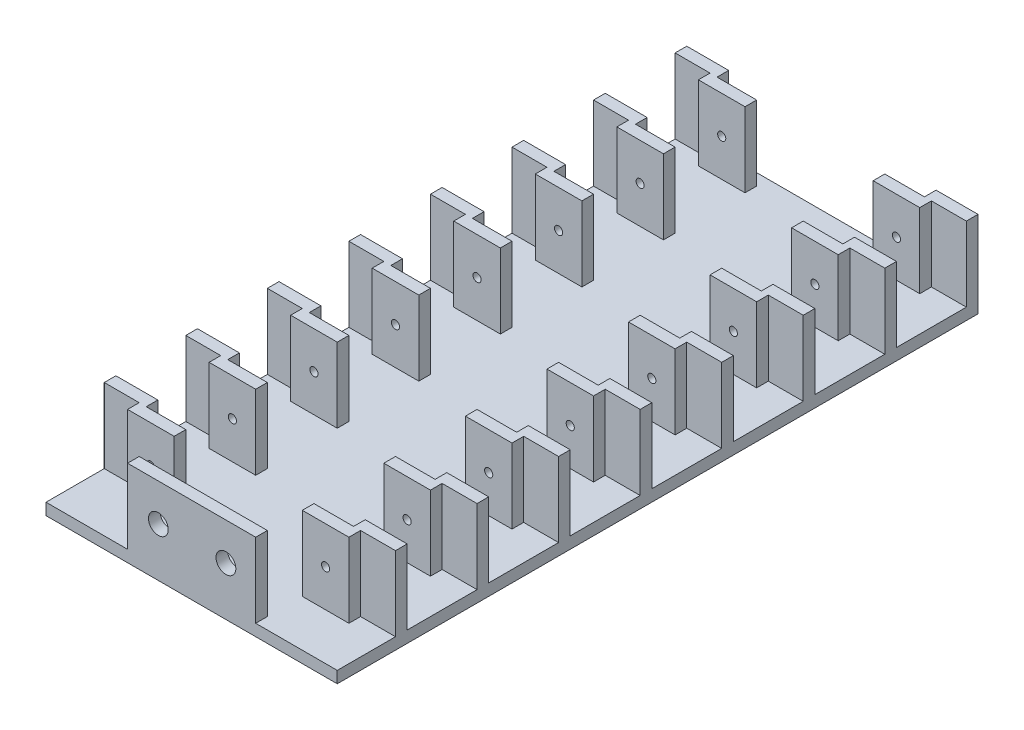
SolidWorks part; units mm, degrees
ref_plane "Front Plane" through (0, 0, 0) normal (0, 0, 1) x (1, 0, 0)
ref_plane "Top Plane" through (0, 0, 0) normal (0, 1, 0) x (1, 0, 0)
ref_plane "Right Plane" through (0, 0, 0) normal (1, 0, 0) x (0, 0, -1)
sketch "Sketch1" plane through (0, 0, 0) normal (0, 1, 0) x (1, 0, 0)
  line L0 (0, -138) -> (0, 138) construction
  line L1 (-14.5, 135) -> (-37.5, 135)
  line L2 (14.5, -135) -> (-14.5, -135)
  line L3 (14.5, -135) -> (14.5, 135) construction
  line L4 (14.5, 135) -> (-14.5, 135)
  line L5 (-14.5, -135) -> (-14.5, 135) construction
  line L6 (14.5, -135) -> (-14.5, 135) construction
  line L7 (14.5, 135) -> (-14.5, -135) construction
  line L8 (-37.5, 135) -> (-37.5, -135) construction
  line L9 (-37.5, -135) -> (-14.5, -135)
  line L10 (-37.5, 135) -> (-62.5, 135)
  line L11 (-62.5, 135) -> (-62.5, -135)
  line L12 (-62.5, -135) -> (-37.5, -135)
  line L13 (37.5, -135) -> (14.5, -135)
  line L14 (62.5, -135) -> (37.5, -135)
  line L15 (62.5, 135) -> (62.5, -135)
  line L16 (37.5, 135) -> (37.5, -135) construction
  line L17 (14.5, 135) -> (37.5, 135)
  line L18 (37.5, 135) -> (62.5, 135)
  point P0 (0, 0)
  point P4 (0, 0)
  dimension "D1" = 276
  dimension "D2" = 29
  dimension "D3" = 23
  dimension "D4" = 125
extrude "Boss-Extrude1" add sketch "Sketch1" along normal blind 5
sketch "Sketch2" plane through (0, 5, 0) normal (0, 1, 0) x (1, 0, 0)
  line L0 (62.5, -135) -> (62.5, 135) construction
  line L1 (-62.5, -135) -> (62.5, -135)
  line L2 (-62.5, -135) -> (-62.5, -130)
  line L3 (-62.5, -130) -> (62.5, -130)
  line L4 (62.5, -135) -> (62.5, -130)
  line L5 (-62.5, 135) -> (-37.5, 135) construction
  line L6 (-62.5, 135) -> (62.5, 135) construction
  line L7 (-62.5, 135) -> (-62.5, 130) construction
  line L8 (-62.5, 130) -> (62.5, 130) construction
  line L9 (62.5, 135) -> (62.5, 130) construction
  line L10 (-37.5, 135) -> (-27.5, 135)
  line L11 (-37.5, 135) -> (-47.5, 135)
  line L12 (-47.5, 135) -> (-47.5, 130)
  line L13 (-47.5, 130) -> (-27.5, 130)
  line L14 (-27.5, 130) -> (-27.5, 135)
  line L15 (0, 135) -> (0, 130) construction
  line L16 (47.5, 130) -> (27.5, 130)
  line L17 (47.5, 135) -> (47.5, 130)
  line L18 (37.5, 135) -> (47.5, 135)
  line L19 (37.5, 135) -> (27.5, 135)
  line L20 (27.5, 130) -> (27.5, 135)
  line L21 (-27.5, 130) -> (-27.5, -130) construction
  dimension "D1" = 5
  dimension "D2" = 5
  dimension "D3" = 25
  dimension "D4" = 10
  dimension "D5" = 10
extrude "Boss-Extrude2" add sketch "Sketch2" along normal blind 32
sketch "Sketch3" plane through (0, 0, 135) normal (0, 0, 1) x (1, 0, 0)
  line L0 (0, 37) -> (0, 0) construction
  line L1 (-62.5, 37) -> (62.5, 37) construction
  line L2 (-62.5, 37) -> (-62.5, 5) construction
  line L5 (-62.5, 37) -> (-62.5, 0) construction
  line L6 (-62.5, 21) -> (62.5, 21) construction
  line L7 (62.5, 37) -> (62.5, 0) construction
  circle A0 centre (-14.2829, 21) radius 4.25
  circle A1 centre (14.7171, 21) radius 4.25
  point P15 (0, 18.5)
  dimension "D1" = 8.5
  dimension "D2" = 8.5
  dimension "D3" = 29
  dimension "D4" = 14.5
  dimension "D5" = 32
  dimension "D6" = 16
extrude "Cut-Extrude1" cut sketch "Sketch3" against normal blind 286 contours A0 | A1
sketch "Sketch8" plane through (0, 0, -130) normal (0, 0, 1) x (1, 0, 0)
  line L0 (0, 37) -> (0, 5) construction
  line L1 (-62.5, 37) -> (62.5, 37) construction
  line L2 (0, 21) -> (-62.5, 21) construction
  line L3 (-62.5, 37) -> (-62.5, 0) construction
  line L4 (-37.5, 37) -> (-37.5, 5) construction
  line L5 (-47.5, 37) -> (-27.5, 37) construction
  line L6 (-47.5, 5) -> (-27.5, 5) construction
  circle A0 centre (-37.5, 21) radius 1.75
  circle A1 centre (37.5, 21) radius 1.75
  dimension "D2" = 3.5
  dimension "D1" = 32
sketch "Sketch9" plane through (0, 0, -135) normal (0, 0, -1) x (-1, 0, 0)
  line L1 (-62.5, 5) -> (62.5, 5)
  line L2 (-62.5, 5) -> (-62.5, 0)
  line L3 (-62.5, 0) -> (62.5, 0)
  line L4 (62.5, 5) -> (62.5, 0)
extrude "Boss-Extrude4" add sketch "Sketch9" along normal blind 5
sketch "Sketch10" plane through (0, 5, 0) normal (0, 1, 0) x (1, 0, 0)
  line L0 (-27.5, 135) -> (-47.5, 135) construction
  line L1 (-62.5, 140) -> (-44.5, 140)
  line L2 (-62.5, 140) -> (-62.5, 135)
  line L3 (-62.5, 135) -> (-44.5, 135)
  line L4 (-44.5, 140) -> (-44.5, 135)
  line L5 (27.5, 135) -> (47.5, 135) construction
  line L6 (62.5, 140) -> (44.5, 140)
  line L7 (62.5, 140) -> (62.5, 135)
  line L8 (62.5, 135) -> (44.5, 135)
  line L9 (44.5, 140) -> (44.5, 135)
  line L10 (-47.5, 135) -> (-47.5, 130) construction
  line L11 (47.5, 130) -> (47.5, 135) construction
  dimension "D1" = 3
  dimension "D2" = 3
extrude "Boss-Extrude8" add sketch "Sketch10" along normal blind 32
sketch "Sketch11" plane through (0, 5, 0) normal (0, 1, 0) x (1, 0, 0)
  line L0 (0, 140) -> (0, -130) construction
  line L1 (-44.5, 140) -> (44.5, 140) construction
  line L2 (62.5, -130) -> (-62.5, -130) construction
  line L3 (-62.5, 140) -> (-62.5, 135) construction
  line L4 (-62.5, 135) -> (-47.5, 135) construction
  line L5 (-47.5, 135) -> (-47.5, 130) construction
  line L6 (-47.5, 130) -> (-27.5, 130) construction
  line L7 (-27.5, 130) -> (-27.5, 135) construction
  line L8 (-27.5, 135) -> (-44.5, 135) construction
  line L9 (-44.5, 135) -> (-44.5, 140) construction
  line L10 (-44.5, 140) -> (-62.5, 140) construction
  line L11 (-27.5, -130) -> (-27.5, -109.8199)
  line L12 (-44.5, 105) -> (-62.5, 105)
  line L13 (-62.5, 105) -> (-62.5, 100)
  line L14 (-62.5, 100) -> (-47.5, 100)
  line L15 (-47.5, 100) -> (-47.5, 95)
  line L16 (-47.5, 95) -> (-27.5, 95)
  line L17 (-27.5, 95) -> (-27.5, 100)
  line L18 (-27.5, 100) -> (-44.5, 100)
  line L19 (-44.5, 100) -> (-44.5, 105)
  line L20 (-44.5, 70) -> (-62.5, 70)
  line L21 (-62.5, 70) -> (-62.5, 65)
  line L22 (-62.5, 65) -> (-47.5, 65)
  line L23 (-47.5, 65) -> (-47.5, 60)
  line L24 (-47.5, 60) -> (-27.5, 60)
  line L25 (-27.5, 60) -> (-27.5, 65)
  line L26 (-27.5, 65) -> (-44.5, 65)
  line L27 (-44.5, 65) -> (-44.5, 70)
  line L28 (-44.5, 35) -> (-62.5, 35)
  line L29 (-62.5, 35) -> (-62.5, 30)
  line L30 (-62.5, 30) -> (-47.5, 30)
  line L31 (-47.5, 30) -> (-47.5, 25)
  line L32 (-47.5, 25) -> (-27.5, 25)
  line L33 (-27.5, 25) -> (-27.5, 30)
  line L34 (-27.5, 30) -> (-44.5, 30)
  line L35 (-44.5, 30) -> (-44.5, 35)
  line L36 (-44.5, 0) -> (-62.5, 0)
  line L37 (-62.5, 0) -> (-62.5, -5)
  line L38 (-62.5, -5) -> (-47.5, -5)
  line L39 (-47.5, -5) -> (-47.5, -10)
  line L40 (-47.5, -10) -> (-27.5, -10)
  line L41 (-27.5, -10) -> (-27.5, -5)
  line L42 (-27.5, -5) -> (-44.5, -5)
  line L43 (-44.5, -5) -> (-44.5, 0)
  line L44 (-44.5, -35) -> (-62.5, -35)
  line L45 (-62.5, -35) -> (-62.5, -40)
  line L46 (-62.5, -40) -> (-47.5, -40)
  line L47 (-47.5, -40) -> (-47.5, -45)
  line L48 (-47.5, -45) -> (-27.5, -45)
  line L49 (-27.5, -45) -> (-27.5, -40)
  line L50 (-27.5, -40) -> (-44.5, -40)
  line L51 (-44.5, -40) -> (-44.5, -35)
  line L52 (-44.5, -70) -> (-62.5, -70)
  line L53 (-62.5, -70) -> (-62.5, -75)
  line L54 (-62.5, -75) -> (-47.5, -75)
  line L55 (-47.5, -75) -> (-47.5, -80)
  line L56 (-47.5, -80) -> (-27.5, -80)
  line L57 (-27.5, -80) -> (-27.5, -75)
  line L58 (-27.5, -75) -> (-44.5, -75)
  line L59 (-44.5, -75) -> (-44.5, -70)
  line L60 (-44.5, -105) -> (-62.5, -105)
  line L61 (-62.5, -105) -> (-62.5, -110)
  line L62 (-62.5, -110) -> (-47.5, -110)
  line L63 (-47.5, -110) -> (-47.5, -115)
  line L64 (-47.5, -115) -> (-27.5, -115)
  line L65 (-27.5, -115) -> (-27.5, -110)
  line L66 (-27.5, -110) -> (-44.5, -110)
  line L67 (-44.5, -110) -> (-44.5, -105)
  line L68 (44.5, -110) -> (44.5, -105)
  line L69 (27.5, -110) -> (44.5, -110)
  line L70 (27.5, -115) -> (27.5, -110)
  line L71 (47.5, -115) -> (27.5, -115)
  line L72 (47.5, -110) -> (47.5, -115)
  line L73 (62.5, -110) -> (47.5, -110)
  line L74 (62.5, -105) -> (62.5, -110)
  line L75 (44.5, -105) -> (62.5, -105)
  line L76 (44.5, -75) -> (44.5, -70)
  line L77 (27.5, -75) -> (44.5, -75)
  line L78 (27.5, -80) -> (27.5, -75)
  line L79 (47.5, -80) -> (27.5, -80)
  line L80 (47.5, -75) -> (47.5, -80)
  line L81 (62.5, -75) -> (47.5, -75)
  line L82 (62.5, -70) -> (62.5, -75)
  line L83 (44.5, -70) -> (62.5, -70)
  line L84 (44.5, -40) -> (44.5, -35)
  line L85 (27.5, -40) -> (44.5, -40)
  line L86 (27.5, -45) -> (27.5, -40)
  line L87 (47.5, -45) -> (27.5, -45)
  line L88 (47.5, -40) -> (47.5, -45)
  line L89 (62.5, -40) -> (47.5, -40)
  line L90 (62.5, -35) -> (62.5, -40)
  line L91 (44.5, -35) -> (62.5, -35)
  line L92 (44.5, -5) -> (44.5, 0)
  line L93 (27.5, -5) -> (44.5, -5)
  line L94 (27.5, -10) -> (27.5, -5)
  line L95 (47.5, -10) -> (27.5, -10)
  line L96 (47.5, -5) -> (47.5, -10)
  line L97 (62.5, -5) -> (47.5, -5)
  line L98 (62.5, 0) -> (62.5, -5)
  line L99 (44.5, 0) -> (62.5, 0)
  line L100 (44.5, 30) -> (44.5, 35)
  line L101 (27.5, 30) -> (44.5, 30)
  line L102 (27.5, 25) -> (27.5, 30)
  line L103 (47.5, 25) -> (27.5, 25)
  line L104 (47.5, 30) -> (47.5, 25)
  line L105 (62.5, 30) -> (47.5, 30)
  line L106 (62.5, 35) -> (62.5, 30)
  line L107 (44.5, 35) -> (62.5, 35)
  line L108 (44.5, 65) -> (44.5, 70)
  line L109 (27.5, 65) -> (44.5, 65)
  line L110 (27.5, 60) -> (27.5, 65)
  line L111 (47.5, 60) -> (27.5, 60)
  line L112 (47.5, 65) -> (47.5, 60)
  line L113 (62.5, 65) -> (47.5, 65)
  line L114 (62.5, 70) -> (62.5, 65)
  line L115 (44.5, 70) -> (62.5, 70)
  line L116 (44.5, 100) -> (44.5, 105)
  line L117 (27.5, 100) -> (44.5, 100)
  line L118 (27.5, 95) -> (27.5, 100)
  line L119 (47.5, 95) -> (27.5, 95)
  line L120 (47.5, 100) -> (47.5, 95)
  line L121 (62.5, 100) -> (47.5, 100)
  line L122 (62.5, 105) -> (62.5, 100)
  line L123 (44.5, 105) -> (62.5, 105)
  line M11 (-62.5, 135) -> (-62.5, -130)
  line M13 (62.5, -130) -> (62.5, 135)
  dimension "D1" = 20.1801
  dimension "D2" = 8
extrude "Boss-Extrude9" add sketch "Sketch11" along normal blind 32 contours L18 L19 L12 L14 L15 L16 L17 M11 | L26 L27 L20 L22 L23 L24 L25 M11 | L34 L35 L28 L30 L31 L32 L33 M11 | L42 L43 L36 L38 L39 L40 L41 M11 | L50 L51 L44 L46 L47 L48 L49 M11 | L58 L59 L52 L54 L55 L56 L57 M11 | L66 L67 L60 L62 L63 L64 L11 M11 | L75 L68 L69 L70 L71 L72 L73 M13 | L83 L76 L77 L78 L79 L80 L81 M13 | L91 L84 L85 L86 L87 L88 L89 M13 | L107 L100 L101 L102 L103 L104 L105 M13 | L115 L108 L109 L110 L111 L112 L113 M13 | L123 L116 L117 L118 L119 L120 L121 M13 | L93 L92 L99 L98 L97 L96 L95 L94 region at (-45.0789, 5, 110.1316) region at (-45.0789, 5, -99.8684) region at (-45.0789, 5, -64.8684) region at (-45.0789, 5, -29.8684) region at (-45.0789, 5, 5.1316) region at (-45.0789, 5, 40.1316) region at (-45.0789, 5, 75.1316) region at (45.0789, 5, -99.8684) region at (45.0789, 5, -64.8684) region at (45.0789, 5, -29.8684) region at (45.0789, 5, 40.1316) region at (45.0789, 5, 75.1316) region at (45.0789, 5, 110.1316)
extrude "Cut-Extrude4" cut sketch "Sketch8" against normal blind 32 and the other way blind 250
sketch "Sketch13" plane through (0, 0, 135) normal (0, 0, 1) x (1, 0, 0)
  line L0 (-62.5, 37) -> (-62.5, 5)
  line L1 (-62.5, 37) -> (-62.5, 0) construction
  line L2 (-62.5, 37) -> (-27.5, 37)
  line L3 (-62.5, 37) -> (62.5, 37) construction
  line L4 (-27.5, 37) -> (-27.5, 5)
  line L5 (-27.5, 5) -> (-62.5, 5)
  line L6 (0, 37) -> (0, 5.5161) construction
  line L7 (27.5, 37) -> (27.5, 5)
  line L8 (62.5, 37) -> (27.5, 37)
  line L9 (62.5, 37) -> (62.5, 5)
  line L10 (27.5, 5) -> (62.5, 5)
  dimension "D1" = 32
  dimension "D2" = 35
extrude "Cut-Extrude5" cut sketch "Sketch13" against normal blind 11
